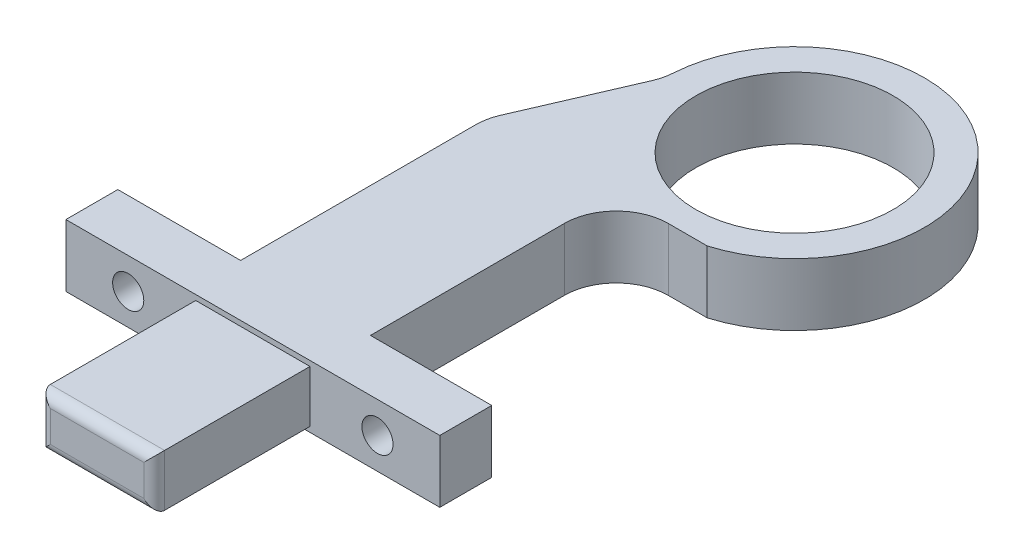
SolidWorks part; units mm, degrees
ref_plane "Alzado" through (0, 0, 0) normal (0, 0, 1) x (1, 0, 0)
ref_plane "Planta" through (0, 0, 0) normal (0, 1, 0) x (1, 0, 0)
ref_plane "Vista lateral" through (0, 0, 0) normal (1, 0, 0) x (0, 0, -1)
sketch "Croquis1" plane through (0, 0, 0) normal (0, 1, 0) x (1, 0, 0)
  line L0 (-12.5, 0) -> (-53.5222, 0) construction
  line L1 (0, 0) -> (-12.5, 21.6506) construction
  line L2 (-29.7673, 10.6211) -> (-25.3747, 20.7837)
  line L3 (-24, -34) -> (-24, -19) construction
  line L4 (-30.1777, -19) -> (-17.6777, -19)
  line L8 (-29.5, -19) -> (-18.5, -19)
  line L9 (-29.5, -19) -> (-29.5, -34)
  line L10 (-29.5, -34) -> (-18.5, -34)
  line L11 (-18.5, -19) -> (-18.5, -34)
  line L12 (-42, -14) -> (-27, -14) construction
  line L13 (-10.5, -14) -> (-6, -14) construction
  line L14 (-42, -14) -> (-27, -14)
  line L15 (-42, -14) -> (-42, -19)
  line L16 (-42, -19) -> (-30.1777, -19)
  line L18 (-6, -14) -> (-10.5, -14)
  line L19 (-6, -14) -> (-6, -19)
  line L20 (-6, -19) -> (-17.6777, -19)
  line L21 (-17.6777, -14) -> (-30.1777, -14)
  line L22 (-17.6777, -14) -> (-17.6777, 4.6717)
  line L23 (-17.6777, 9.6717) -> (-30.1777, 9.6717)
  line L24 (-30.1777, -14) -> (-30.1777, 8.6374)
  line L25 (-8.9286, 9.6717) -> (-12.6777, 9.6717)
  line L26 (-10.5, -14) -> (-17.6777, -14)
  arc A1 (-8.9286, 9.6717) -> (-24.9745, 22.4484) centre (-12.5, 21.6506) ccw
  circle A2 centre (-12.5, 21.6506) radius 9.5
  arc A6 (-30.1777, 8.6374) -> (-29.7673, 10.6211) centre (-25.1777, 8.6374) cw
  arc A7 (-24.9745, 22.4484) -> (-25.3747, 20.7837) centre (-29.9643, 22.7675) cw
  arc A8 (-17.6777, 4.6717) -> (-12.6777, 9.6717) centre (-12.6777, 4.6717) cw
  point P31 (-25, 21.6506)
  dimension "D3" = 25
  dimension "D4" = 5
  dimension "D5" = 19
  dimension "D1" = 25
  dimension "D2" = 60
  dimension "D7" = 11
  dimension "D8" = 15
  dimension "D9" = 24
  dimension "D10" = 5
  dimension "D11" = 18
  dimension "D12" = 18
extrude "Saliente-Extruir1" add sketch "Croquis1" along normal blind 6 contours A1 L14 L15 L16 L4 L20 L19 L18 A2 | L11 L4 L9 L10 | L22 A8 L25 A1 A7 L2 A6 L24 L14 L21 A2 region at (-19.8053, 0, -8.218) region at (-24, 0, 16.5) region at (-24, 0, 26.5)
sketch "Croquis2" plane through (0, 0, 19) normal (0, 0, 1) x (1, 0, 0)
  line L0 (-42, 3) -> (-6, 3) construction
  line L1 (-42, 6) -> (-42, 0) construction
  line L2 (-6, 6) -> (-6, 0) construction
  line L3 (-24, 6) -> (-24, 0) construction
  line L4 (-29.5, 6) -> (-18.5, 6) construction
  line L5 (-29.5, 0) -> (-18.5, 0) construction
  circle A0 centre (-36, 3) radius 1.5
  circle A1 centre (-12, 3) radius 1.5
  dimension "D3" = 3
  dimension "D4" = 3
  dimension "D1" = 12
  dimension "D2" = 12
extrude "Cortar-Extruir1" cut sketch "Croquis2" against normal blind 6
sketch "Croquis3" plane through (0, 6, 0) normal (0, 1, 0) x (1, 0, 0)
  line L1 (-18.5, -34) -> (-29.5, -34)
  line L2 (-18.5, -34) -> (-18.5, -19)
  line L3 (-18.5, -19) -> (-29.5, -19)
  line L4 (-29.5, -34) -> (-29.5, -19)
extrude "Cortar-Extruir2" cut sketch "Croquis3" against normal blind 0.5
sketch "Croquis4" plane through (0, 0, 0) normal (0, -1, 0) x (1, 0, 0)
  line L1 (-29.5, 34) -> (-18.5, 34)
  line L2 (-29.5, 34) -> (-29.5, 19)
  line L3 (-29.5, 19) -> (-18.5, 19)
  line L4 (-18.5, 34) -> (-18.5, 19)
extrude "Cortar-Extruir3" cut sketch "Croquis4" against normal blind 0.5
fillet "Redondeo1" radius 1 4 edges at (-29.5, 3, 34) (-24, 5.5, 34) (-18.5, 3, 34) (-24, 0.5, 34)
